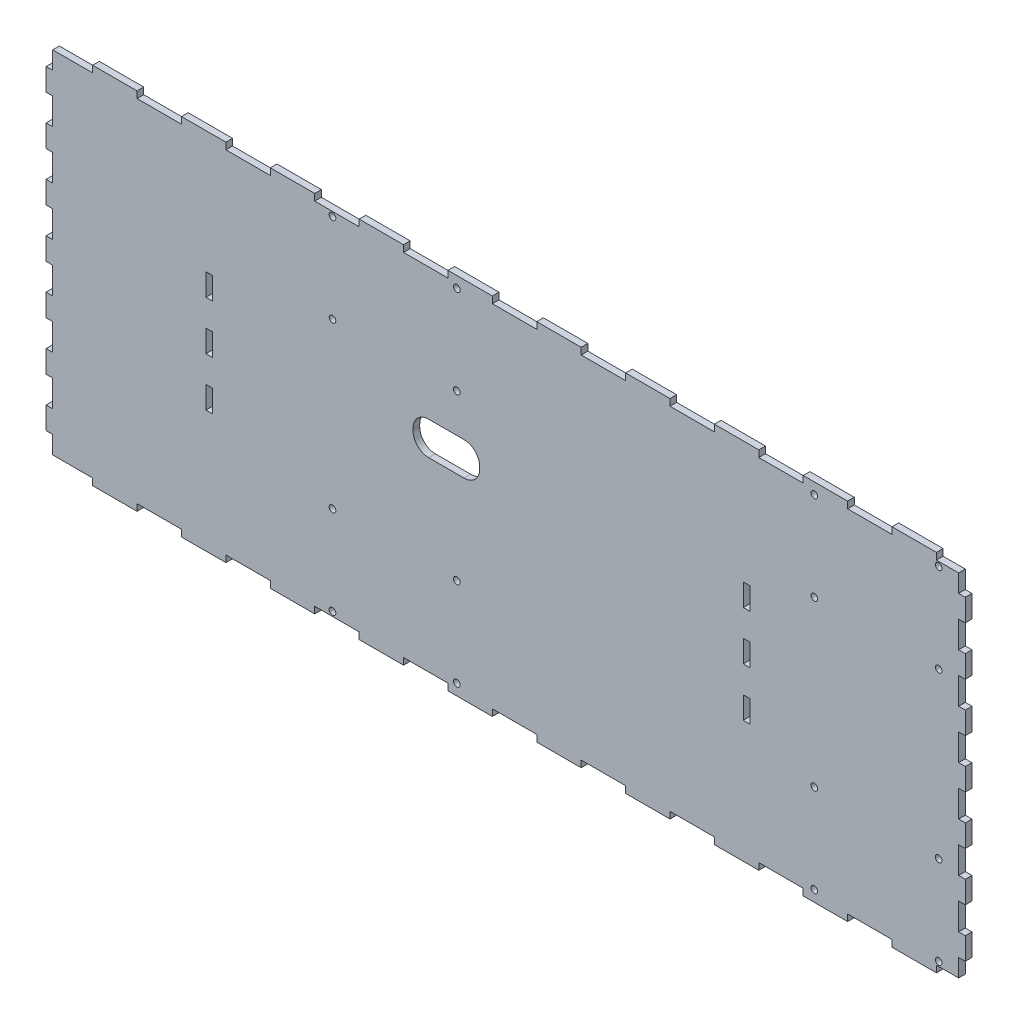
SolidWorks part; units mm, degrees
material "birch 3mm plywood"
ref_plane "Front Plane" through (0, 0, 0) normal (0, 0, 1) x (1, 0, 0)
ref_plane "Top Plane" through (0, 0, 0) normal (0, 1, 0) x (1, 0, 0)
ref_plane "Right Plane" through (0, 0, 0) normal (1, 0, 0) x (0, 0, -1)
sketch "Sketch1" plane through (0, 0, 152) normal (0, 0, 1) x (1, 0, 0)
  line L1 (-207, 82) -> (207, 82)
  line L2 (-207, 82) -> (-207, -82)
  line L3 (-207, -82) -> (207, -82)
  line L4 (207, 82) -> (207, -82)
  line L12 (200, -75) -> (-200, -75) construction
  line L13 (200, 75) -> (200, -75) construction
  line L14 (-200, -75) -> (-200, 75) construction
  line L15 (-200, 75) -> (200, 75) construction
  line L26 (-200, 0) -> (200, 0) construction
  line L31 (-200, 0) -> (200, 0) construction
  point P14 (0, 0)
  point P15 (0, 0)
  point P32 (-47.5, -25.9413)
  point P35 (256.981, -145.9413)
  point P38 (10.8894, 25.9413)
  point P51 (10.8894, -25.9413)
  point P54 (256.981, 145.9413)
  dimension "D1" = 7
  dimension "D2" = 7
  dimension "D3" = 7
  dimension "D4" = 7
  dimension "D5" = 150
  dimension "D6" = 400
extrude "Boss-Extrude1" add sketch "Sketch1" along normal blind 3
sketch "Sketch2" plane through (-207, 0, 0) normal (-1, 0, 0) x (0, 0, 1)
  line L7 (155, -82) -> (152, -82)
  line L8 (152, -82) -> (152, -71)
  line L9 (152, 82) -> (155, 82)
  line L10 (155, 82) -> (155, 71)
  line L11 (152, -61) -> (152, -49)
  line L12 (155, -71) -> (155, -82)
  line L13 (155, -49) -> (155, -61)
  line L14 (152, -39) -> (152, -27)
  line L15 (152, -17) -> (152, -5)
  line L16 (155, -27) -> (155, -39)
  line L17 (155, -5) -> (155, -17)
  line L18 (152, 5) -> (152, 17)
  line L19 (152, 27) -> (152, 39)
  line L20 (155, 17) -> (155, 5)
  line L21 (155, 39) -> (155, 27)
  line L22 (152, 49) -> (152, 61)
  line L23 (152, 71) -> (152, 82)
  line L24 (155, 61) -> (155, 49)
  line L76 (132.5, 88.6) -> (132.5, 93.6)
  line L77 (132.5, 88.6) -> (132.5, 93.6)
  line L78 (129.5, 98.6) -> (128.8771, 98.6)
  line L79 (129.5, 98.6) -> (128.8771, 98.6)
  line L80 (129.5, 82) -> (129.5, 88.6)
  line L81 (129.5, 82) -> (129.5, 88.6)
  line L82 (129.5, 88.6) -> (132.5, 88.6)
  line L83 (129.5, 88.6) -> (132.5, 88.6)
  line L85 (16, 82) -> (16, -82)
  line L102 (129.5, -82) -> (133, -82)
  line L103 (133, -82) -> (133, -79)
  line L104 (133, -79) -> (145, -79)
  line L105 (145, -79) -> (145, -82)
  line L106 (145, -82) -> (155, -82)
  line L107 (155, -82) -> (155, -71)
  line L108 (155, -71) -> (152, -71)
  line L109 (152, -71) -> (152, -61)
  line L110 (152, -61) -> (155, -61)
  line L111 (155, -61) -> (155, -49)
  line L112 (155, -49) -> (152, -49)
  line L113 (152, -49) -> (152, -39)
  line L114 (152, -39) -> (155, -39)
  line L115 (155, -39) -> (155, -27)
  line L116 (155, -27) -> (152, -27)
  line L117 (152, -27) -> (152, -17)
  line L118 (152, -17) -> (155, -17)
  line L119 (155, -17) -> (155, -5)
  line L120 (155, -5) -> (152, -5)
  line L121 (152, -5) -> (152, 5)
  line L122 (152, 5) -> (155, 5)
  line L123 (155, 5) -> (155, 17)
  line L124 (155, 17) -> (152, 17)
  line L125 (152, 17) -> (152, 27)
  line L126 (152, 27) -> (155, 27)
  line L127 (155, 27) -> (155, 39)
  line L128 (155, 39) -> (152, 39)
  line L129 (152, 39) -> (152, 49)
  line L130 (152, 49) -> (155, 49)
  line L131 (155, 49) -> (155, 61)
  line L132 (155, 61) -> (152, 61)
  line L133 (152, 61) -> (152, 71)
  line L134 (152, 71) -> (155, 71)
  line L135 (155, 71) -> (155, 82)
  line L136 (155, 82) -> (145, 82)
  line L137 (145, 82) -> (145, 79)
  line L138 (145, 79) -> (133, 79)
  line L139 (133, 79) -> (133, 82)
  line L140 (133, 82) -> (129.5, 82)
  line L184 (155, -71) -> (152, -71)
  line L186 (152, -61) -> (155, -61)
  line L188 (155, -49) -> (152, -49)
  line L190 (152, -39) -> (155, -39)
  line L192 (155, -27) -> (152, -27)
  line L194 (152, -17) -> (155, -17)
  line L196 (155, -5) -> (152, -5)
  line L198 (152, 5) -> (155, 5)
  line L200 (155, 17) -> (152, 17)
  line L202 (152, 27) -> (155, 27)
  line L204 (155, 39) -> (152, 39)
  line L206 (152, 49) -> (155, 49)
  line L208 (155, 61) -> (152, 61)
  line L210 (152, 71) -> (155, 71)
  line L297 (132.5, 93.6) -> (129.5, 93.6)
  line L298 (132.5, 93.6) -> (129.5, 93.6)
  line L299 (129.5, 93.6) -> (129.5, 98.6)
  line L300 (129.5, 93.6) -> (129.5, 98.6)
  line L301 (128.8771, -98.6) -> (129.5, -98.6)
  line L302 (128.8771, -98.6) -> (129.5, -98.6)
  line L303 (129.5, -98.6) -> (129.5, -93.6)
  line L304 (129.5, -98.6) -> (129.5, -93.6)
  line L305 (129.5, -93.6) -> (132.5, -93.6)
  line L306 (129.5, -93.6) -> (132.5, -93.6)
  line L307 (132.5, -93.6) -> (132.5, -88.6)
  line L308 (132.5, -93.6) -> (132.5, -88.6)
  line L309 (132.5, -88.6) -> (129.5, -88.6)
  line L310 (132.5, -88.6) -> (129.5, -88.6)
  line L311 (129.5, -88.6) -> (129.5, -82)
  line L312 (129.5, -88.6) -> (129.5, -82)
  arc A4 (128.8771, 98.6) -> (16, 82) centre (128.8771, -293.4723) ccw
  arc A5 (128.8771, 98.6) -> (16, 82) centre (128.8771, -293.4723) ccw
  arc A6 (16, -82) -> (128.8771, -98.6) centre (128.8771, 293.4723) ccw
  arc A7 (16, -82) -> (128.8771, -98.6) centre (128.8771, 293.4723) ccw
  line M77 (152, 82) -> (152, -82)
  line M78 (152, -82) -> (155, -82)
  line M79 (155, -82) -> (155, 82)
  line M80 (155, 82) -> (152, 82)
  dimension "D1" = 0
extrude "Cut-Extrude1" cut sketch "Sketch2" against normal blind 3 contours L184 M79 M77 M78 | L188 L186 M79 M77 | L192 L190 M79 M77 | L196 L194 M79 M77 | L200 L198 M79 M77 | L204 L202 M79 M77 | L208 L206 M79 M77 | L210 M77 M79 M80 region at (-207, -76.5, 153.5) region at (-207, -55, 153.5) region at (-207, -33, 153.5) region at (-207, -11, 153.5) region at (-207, 11, 153.5) region at (-207, 33, 153.5) region at (-207, 55, 153.5) region at (-207, 76.5, 153.5)
mirror "Mirror1" about plane through (0, 0, 0) normal (1, 0, 0) of "Cut-Extrude1"
sketch "Sketch3" plane through (0, 82, 0) normal (0, 1, 0) x (1, 0, 0)
  line L92 (174, -152) -> (194, -152)
  line L93 (194, -152) -> (194, -155)
  line L94 (194, -155) -> (204, -155)
  line L97 (207, -45) -> (204, -45)
  line L120 (204, -16) -> (-204, -16)
  line L123 (-204, -45) -> (-207, -45)
  line L146 (-204, -155) -> (-186, -155)
  line L147 (-186, -155) -> (-186, -152)
  line L148 (-186, -152) -> (-166, -152)
  line L149 (-166, -152) -> (-166, -155)
  line L150 (-166, -155) -> (-146, -155)
  line L151 (-146, -155) -> (-146, -152)
  line L152 (-146, -152) -> (-126, -152)
  line L153 (-126, -152) -> (-126, -155)
  line L154 (-126, -155) -> (-106, -155)
  line L155 (-106, -155) -> (-106, -152)
  line L156 (-106, -152) -> (-86, -152)
  line L157 (-86, -152) -> (-86, -155)
  line L158 (-86, -155) -> (-66, -155)
  line L159 (-66, -155) -> (-66, -152)
  line L160 (-66, -152) -> (-46, -152)
  line L161 (-46, -152) -> (-46, -155)
  line L162 (-46, -155) -> (-26, -155)
  line L163 (-26, -155) -> (-26, -152)
  line L164 (-26, -152) -> (-6, -152)
  line L165 (-6, -152) -> (-6, -155)
  line L166 (-6, -155) -> (14, -155)
  line L167 (14, -155) -> (14, -152)
  line L168 (14, -152) -> (34, -152)
  line L169 (34, -152) -> (34, -155)
  line L170 (34, -155) -> (54, -155)
  line L171 (54, -155) -> (54, -152)
  line L172 (54, -152) -> (74, -152)
  line L173 (74, -152) -> (74, -155)
  line L174 (74, -155) -> (94, -155)
  line L175 (94, -155) -> (94, -152)
  line L176 (94, -152) -> (114, -152)
  line L177 (114, -152) -> (114, -155)
  line L178 (114, -155) -> (134, -155)
  line L179 (134, -155) -> (134, -152)
  line L180 (134, -152) -> (154, -152)
  line L181 (154, -152) -> (154, -155)
  line L182 (154, -155) -> (174, -155)
  line L183 (174, -155) -> (174, -152)
  line L184 (174, -152) -> (194, -152)
  line L185 (194, -152) -> (194, -155)
  line L186 (194, -155) -> (204, -155)
  line L212 (204, -16) -> (-204, -16)
  line L238 (-204, -155) -> (-186, -155)
  line L239 (-186, -155) -> (-186, -152)
  line L240 (-186, -152) -> (-166, -152)
  line L241 (-166, -152) -> (-166, -155)
  line L242 (-166, -155) -> (-146, -155)
  line L243 (-146, -155) -> (-146, -152)
  line L244 (-146, -152) -> (-126, -152)
  line L245 (-126, -152) -> (-126, -155)
  line L246 (-126, -155) -> (-106, -155)
  line L247 (-106, -155) -> (-106, -152)
  line L248 (-106, -152) -> (-86, -152)
  line L249 (-86, -152) -> (-86, -155)
  line L250 (-86, -155) -> (-66, -155)
  line L251 (-66, -155) -> (-66, -152)
  line L252 (-66, -152) -> (-46, -152)
  line L253 (-46, -152) -> (-46, -155)
  line L254 (-46, -155) -> (-26, -155)
  line L255 (-26, -155) -> (-26, -152)
  line L256 (-26, -152) -> (-6, -152)
  line L257 (-6, -152) -> (-6, -155)
  line L258 (-6, -155) -> (14, -155)
  line L259 (14, -155) -> (14, -152)
  line L260 (14, -152) -> (34, -152)
  line L261 (34, -152) -> (34, -155)
  line L262 (34, -155) -> (54, -155)
  line L263 (54, -155) -> (54, -152)
  line L264 (54, -152) -> (74, -152)
  line L265 (74, -152) -> (74, -155)
  line L266 (74, -155) -> (94, -155)
  line L267 (94, -155) -> (94, -152)
  line L268 (94, -152) -> (114, -152)
  line L269 (114, -152) -> (114, -155)
  line L270 (114, -155) -> (134, -155)
  line L271 (134, -155) -> (134, -152)
  line L272 (134, -152) -> (154, -152)
  line L273 (154, -152) -> (154, -155)
  line L274 (154, -155) -> (174, -155)
  line L275 (174, -155) -> (174, -152)
  line L576 (-204, -45) -> (-207, -45)
  line L577 (-207, -45) -> (-207, -57)
  line L578 (-207, -45) -> (-207, -57)
  line L579 (-207, -57) -> (-204, -57)
  line L580 (-207, -57) -> (-204, -57)
  line L581 (-204, -57) -> (-204, -67)
  line L582 (-204, -57) -> (-204, -67)
  line L583 (-204, -67) -> (-207, -67)
  line L584 (-204, -67) -> (-207, -67)
  line L585 (-207, -67) -> (-207, -79)
  line L586 (-207, -67) -> (-207, -79)
  line L587 (-207, -79) -> (-204, -79)
  line L588 (-207, -79) -> (-204, -79)
  line L589 (-204, -79) -> (-204, -89)
  line L590 (-204, -79) -> (-204, -89)
  line L591 (-204, -89) -> (-207, -89)
  line L592 (-204, -89) -> (-207, -89)
  line L593 (-207, -89) -> (-207, -101)
  line L594 (-207, -89) -> (-207, -101)
  line L595 (-207, -101) -> (-204, -101)
  line L596 (-207, -101) -> (-204, -101)
  line L597 (-204, -101) -> (-204, -111)
  line L598 (-204, -101) -> (-204, -111)
  line L599 (-204, -111) -> (-207, -111)
  line L600 (-204, -111) -> (-207, -111)
  line L601 (-207, -111) -> (-207, -123)
  line L602 (-207, -111) -> (-207, -123)
  line L603 (-207, -123) -> (-204, -123)
  line L604 (-207, -123) -> (-204, -123)
  line L605 (-204, -123) -> (-204, -133)
  line L606 (-204, -123) -> (-204, -133)
  line L607 (-204, -133) -> (-207, -133)
  line L608 (-204, -133) -> (-207, -133)
  line L609 (-207, -133) -> (-207, -145)
  line L610 (-207, -133) -> (-207, -145)
  line L611 (-207, -145) -> (-204, -145)
  line L612 (-207, -145) -> (-204, -145)
  line L613 (-204, -145) -> (-204, -155)
  line L614 (-204, -145) -> (-204, -155)
  line L615 (-204, -16) -> (-204, -23)
  line L616 (-204, -16) -> (-204, -23)
  line L617 (-204, -23) -> (-207, -23)
  line L618 (-204, -23) -> (-207, -23)
  line L619 (-207, -23) -> (-207, -35)
  line L620 (-207, -23) -> (-207, -35)
  line L621 (-207, -35) -> (-204, -35)
  line L622 (-207, -35) -> (-204, -35)
  line L623 (-204, -35) -> (-204, -45)
  line L624 (-204, -35) -> (-204, -45)
  line L741 (207, -45) -> (204, -45)
  line L742 (204, -45) -> (204, -35)
  line L743 (204, -45) -> (204, -35)
  line L744 (204, -35) -> (207, -35)
  line L745 (204, -35) -> (207, -35)
  line L746 (207, -35) -> (207, -23)
  line L747 (207, -35) -> (207, -23)
  line L748 (207, -23) -> (204, -23)
  line L749 (207, -23) -> (204, -23)
  line L750 (204, -23) -> (204, -16)
  line L751 (204, -23) -> (204, -16)
  line L752 (204, -155) -> (204, -145)
  line L753 (204, -155) -> (204, -145)
  line L754 (204, -145) -> (207, -145)
  line L755 (204, -145) -> (207, -145)
  line L756 (207, -145) -> (207, -133)
  line L757 (207, -145) -> (207, -133)
  line L758 (207, -133) -> (204, -133)
  line L759 (207, -133) -> (204, -133)
  line L760 (204, -133) -> (204, -123)
  line L761 (204, -133) -> (204, -123)
  line L762 (204, -123) -> (207, -123)
  line L763 (204, -123) -> (207, -123)
  line L764 (207, -123) -> (207, -111)
  line L765 (207, -123) -> (207, -111)
  line L766 (207, -111) -> (204, -111)
  line L767 (207, -111) -> (204, -111)
  line L768 (204, -111) -> (204, -101)
  line L769 (204, -111) -> (204, -101)
  line L770 (204, -101) -> (207, -101)
  line L771 (204, -101) -> (207, -101)
  line L772 (207, -101) -> (207, -89)
  line L773 (207, -101) -> (207, -89)
  line L774 (207, -89) -> (204, -89)
  line L775 (207, -89) -> (204, -89)
  line L776 (204, -89) -> (204, -79)
  line L777 (204, -89) -> (204, -79)
  line L778 (204, -79) -> (207, -79)
  line L779 (204, -79) -> (207, -79)
  line L780 (207, -79) -> (207, -67)
  line L781 (207, -79) -> (207, -67)
  line L782 (207, -67) -> (204, -67)
  line L783 (207, -67) -> (204, -67)
  line L784 (204, -67) -> (204, -57)
  line L785 (204, -67) -> (204, -57)
  line L786 (204, -57) -> (207, -57)
  line L787 (204, -57) -> (207, -57)
  line L788 (207, -57) -> (207, -45)
  line L789 (207, -57) -> (207, -45)
  dimension "D1" = 0
extrude "Cut-Extrude2" cut sketch "Sketch3" against normal blind 3
mirror "Mirror2" about plane through (0, 0, 0) normal (0, 1, 0) of "Cut-Extrude2"
sketch "Sketch4" plane through (0, 0, 155) normal (0, 0, 1) x (1, 0, 0)
  line L0 (-132, 27) -> (-132, 17) construction
  line L1 (-132, 17) -> (-135, 17) construction
  line L2 (-135, 17) -> (-135, 27) construction
  line L3 (-135, 27) -> (-132, 27) construction
  line L4 (-132, 5) -> (-132, -5) construction
  line L5 (-132, -5) -> (-135, -5) construction
  line L6 (-135, -5) -> (-135, 5) construction
  line L7 (-135, 5) -> (-132, 5) construction
  line L8 (-132, -17) -> (-132, -27) construction
  line L9 (-132, -27) -> (-135, -27) construction
  line L10 (-135, -27) -> (-135, -17) construction
  line L11 (-135, -17) -> (-132, -17) construction
  line L12 (-132, 27) -> (-132, 17)
  line L13 (-132, 17) -> (-135, 17)
  line L14 (-135, 17) -> (-135, 27)
  line L15 (-135, 27) -> (-132, 27)
  line L16 (-132, 5) -> (-132, -5)
  line L17 (-132, -5) -> (-135, -5)
  line L18 (-135, -5) -> (-135, 5)
  line L19 (-135, 5) -> (-132, 5)
  line L20 (-132, -17) -> (-132, -27)
  line L21 (-132, -27) -> (-135, -27)
  line L22 (-135, -27) -> (-135, -17)
  line L23 (-135, -17) -> (-132, -17)
  line L24 (110, 27) -> (110, 17) construction
  line L25 (110, 17) -> (107, 17) construction
  line L26 (107, 17) -> (107, 27) construction
  line L27 (107, 27) -> (110, 27) construction
  line L28 (110, 5) -> (110, -5) construction
  line L29 (110, -5) -> (107, -5) construction
  line L30 (107, -5) -> (107, 5) construction
  line L31 (107, 5) -> (110, 5) construction
  line L32 (110, -17) -> (110, -27) construction
  line L33 (110, -27) -> (107, -27) construction
  line L34 (107, -27) -> (107, -17) construction
  line L35 (107, -17) -> (110, -17) construction
  line L36 (110, 27) -> (110, 17)
  line L37 (110, 17) -> (107, 17)
  line L38 (107, 17) -> (107, 27)
  line L39 (107, 27) -> (110, 27)
  line L40 (110, 5) -> (110, -5)
  line L41 (110, -5) -> (107, -5)
  line L42 (107, -5) -> (107, 5)
  line L43 (107, 5) -> (110, 5)
  line L44 (110, -17) -> (110, -27)
  line L45 (110, -27) -> (107, -27)
  line L46 (107, -27) -> (107, -17)
  line L47 (107, -17) -> (110, -17)
  line L80 (207, 0) -> (-207, 0) construction
  line L81 (207, -5) -> (207, 5) construction
  line L82 (-207, 5) -> (-207, -5) construction
  circle A0 centre (139, 37) radius 1.5 construction
  circle A1 centre (195, 37) radius 1.5 construction
  circle A2 centre (195, 77) radius 1.5 construction
  circle A3 centre (139, 77) radius 1.5 construction
  circle A4 centre (-78, 77) radius 1.5 construction
  circle A5 centre (-22, 77) radius 1.5 construction
  circle A6 centre (-78, 37) radius 1.5 construction
  circle A7 centre (-22, 37) radius 1.5 construction
  circle A8 centre (139, 37) radius 1.5
  circle A9 centre (195, 37) radius 1.5
  circle A10 centre (195, 77) radius 1.5
  circle A11 centre (139, 77) radius 1.5
  circle A12 centre (-78, 77) radius 1.5
  circle A13 centre (-22, 77) radius 1.5
  circle A14 centre (-78, 37) radius 1.5
  circle A15 centre (-22, 37) radius 1.5
  circle A16 centre (139, -77) radius 1.5
  circle A17 centre (195, -77) radius 1.5
  circle A18 centre (195, -37) radius 1.5
  circle A19 centre (139, -37) radius 1.5
  circle A20 centre (-22, -37) radius 1.5
  circle A21 centre (-78, -37) radius 1.5
  circle A22 centre (-22, -77) radius 1.5
  circle A23 centre (-78, -77) radius 1.5
extrude "Cut-Extrude3" cut sketch "Sketch4" against normal blind 10
sketch "Sketch5" plane through (0, 0, 155) normal (0, 0, 1) x (1, 0, 0)
  line L1 (-34.7, 4.6) -> (-18.7, 4.6)
  line L2 (-41.7, 11.6) -> (-41.7, 12.6)
  line L3 (-34.7, 19.6) -> (-18.7, 19.6)
  line L4 (-11.7, 12.6) -> (-11.7, 11.6)
  line L5 (-27.7, 4.6) -> (0, 4.6) construction
  line L7 (-27.7, 4.6) -> (-27.7, -7.8) construction
  arc A0 (-34.7, 19.6) -> (-41.7, 12.6) centre (-34.7, 12.6) ccw
  arc A1 (-11.7, 12.6) -> (-18.7, 19.6) centre (-18.7, 12.6) ccw
  arc A2 (-18.7, 4.6) -> (-11.7, 11.6) centre (-18.7, 11.6) ccw
  arc A3 (-34.7, 4.6) -> (-41.7, 11.6) centre (-34.7, 11.6) cw
  point P4 (-36.8267, 4.6)
  point P5 (-13.1132, 4.6)
  point P16 (-11.7, 4.6)
  point P19 (-41.7, 4.6)
  dimension "D4" = 7
  dimension "D1" = 30
  dimension "D2" = 15
  dimension "D3" = 16
extrude "Cut-Extrude4" cut sketch "Sketch5" against normal blind 10
